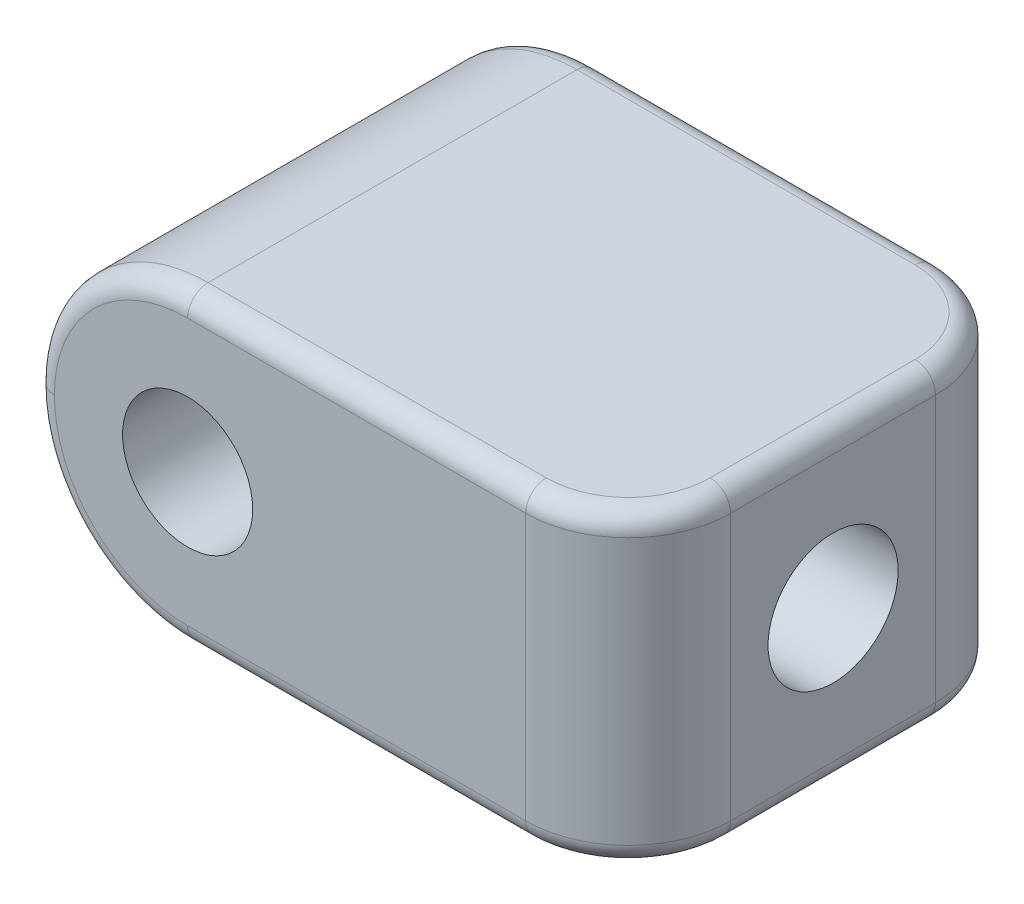
SolidWorks part; units mm, degrees
ref_plane "Front Plane" through (0, 0, 0) normal (0, 0, 1) x (1, 0, 0)
ref_plane "Top Plane" through (0, 0, 0) normal (0, 1, 0) x (1, 0, 0)
ref_plane "Right Plane" through (0, 0, 0) normal (1, 0, 0) x (0, 0, -1)
sketch "Sketch1" plane through (0, 0, 0) normal (0, 1, 0) x (1, 0, 0)
  line L0 (-14.5, 10) -> (14.5, -10) construction
  line L1 (-14.5, 10) -> (14.5, 10)
  line L2 (-14.5, 10) -> (-14.5, -10)
  line L3 (-14.5, -10) -> (14.5, -10)
  line L4 (14.5, 10) -> (14.5, -10)
  dimension "D1" = 20
  dimension "D2" = 29
extrude "Boss-Extrude1" add sketch "Sketch1" along normal mid plane 15
sketch "Sketch2" plane through (0, 0, 10) normal (0, 0, 1) x (1, 0, 0)
  line L1 (-14.5, 7.5) -> (-14.5, -7.5) construction
  circle A0 centre (-7, 0) radius 3.175
  dimension "D1" = 6.35
  dimension "D3" = 7.5
extrude "Cut-Extrude1" cut sketch "Sketch2" against normal through all
fillet "Fillet2" radius 7.5 2 edges at (-14.5, 7.5, 0) (-14.5, -7.5, 0)
sketch "Sketch3" plane through (14.5, 0, 0) normal (1, 0, 0) x (0, 0, -1)
  circle A0 centre (0, 0) radius 3.175
  dimension "D1" = 6.35
extrude "Cut-Extrude2" cut sketch "Sketch3" against normal up to next
fillet "Fillet3" radius 5 2 edges at (14.5, 0, -10) (14.5, 0, 10)
fillet "Fillet4" radius 1 14 edges at (-12.3033, 5.3033, 10) (-12.3033, -5.3033, 10) (1.25, -7.5, 10) (13.0355, -7.5, 8.5355) (14.5, -7.5, 0) (13.0355, -7.5, -8.5355) (1.25, -7.5, -10) (-12.3033, -5.3033, -10) (-12.3033, 5.3033, -10) (1.25, 7.5, -10) (13.0355, 7.5, -8.5355) (14.5, 7.5, 0) (13.0355, 7.5, 8.5355) (1.25, 7.5, 10)
